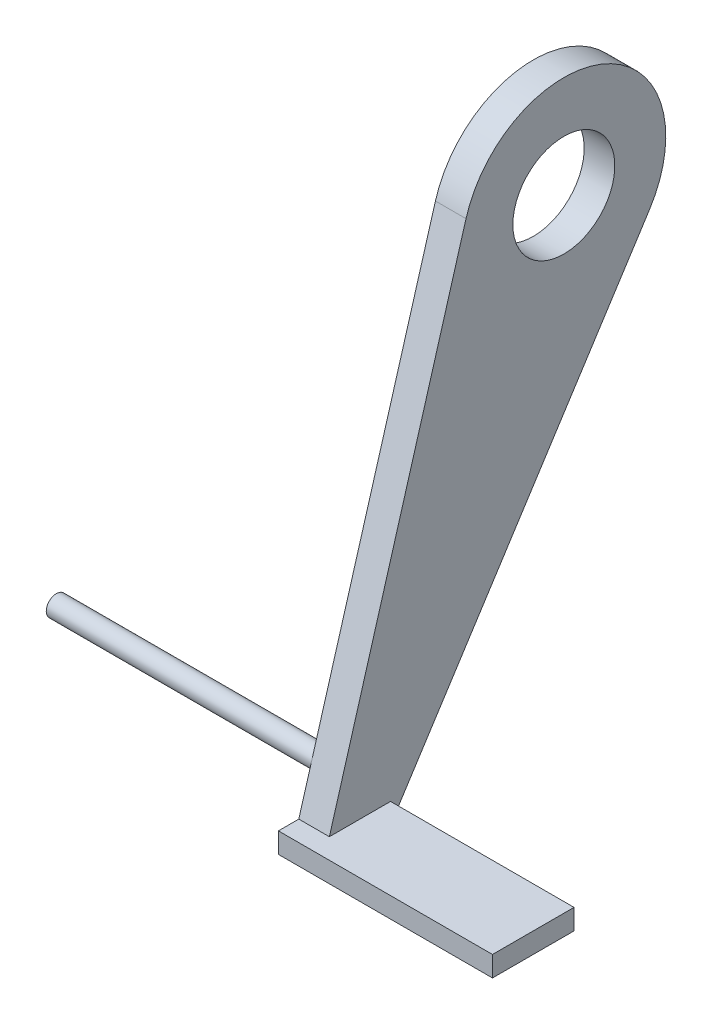
SolidWorks part; units mm, degrees
ref_plane "Front Plane" through (0, 0, 0) normal (0, 0, 1) x (1, 0, 0)
ref_plane "Top Plane" through (0, 0, 0) normal (0, 1, 0) x (1, 0, 0)
ref_plane "Right Plane" through (0, 0, 0) normal (1, 0, 0) x (0, 0, -1)
sketch "Sketch1" plane through (0, 0, 0) normal (1, 0, 0) x (0, 0, -1)
  line L0 (2.1376, -1.372) -> (-4.318, -11.43)
  line L1 (-6.35, -10.922) -> (-4.318, -10.922)
  line L2 (-6.35, -10.922) -> (-6.35, -11.43)
  line L3 (-6.35, -11.43) -> (-4.318, -11.43)
  line L4 (-4.318, -10.922) -> (-4.318, -11.43)
  line L5 (-2.4378, 0.7132) -> (-5.842, -10.922)
  circle A0 centre (0, 0) radius 1.27
  circle A1 centre (0, 0) radius 2.54
  dimension "D1" = 2.54
  dimension "D2" = 5.08
  dimension "D3" = 0.508
  dimension "D4" = 2.032
  dimension "D5" = 11.43
  dimension "D6" = 4.318
  dimension "D7" = 1.524
extrude "Boss-Extrude1" add sketch "Sketch1" along normal blind 5.334 contours L4 L1 L2 L3 region at (0, -11.176, 5.334)
extrude "Boss-Extrude2" add sketch "Sketch1<3>" along normal blind 0.762 contours A1 L5 L1 L4 L0 | A1 A0 region at (0, -5.7206, 2.6113) region at (0, -2.2459, 1.0236)
sketch "Sketch1<3>" plane through (0, 0, 0) normal (1, 0, 0) x (0, 0, -1) same geometry as "Sketch1"
sketch "Sketch2" plane through (0, 0, 0) normal (-1, 0, 0) x (0, 0, 1)
  line L0 (2.4378, 0.7132) -> (5.842, -10.922) construction
  circle A0 centre (5.2768, -9.8948) radius 0.254
  dimension "D1" = 0.508
extrude "Boss-Extrude3" add sketch "Sketch2" along normal blind 6.604
